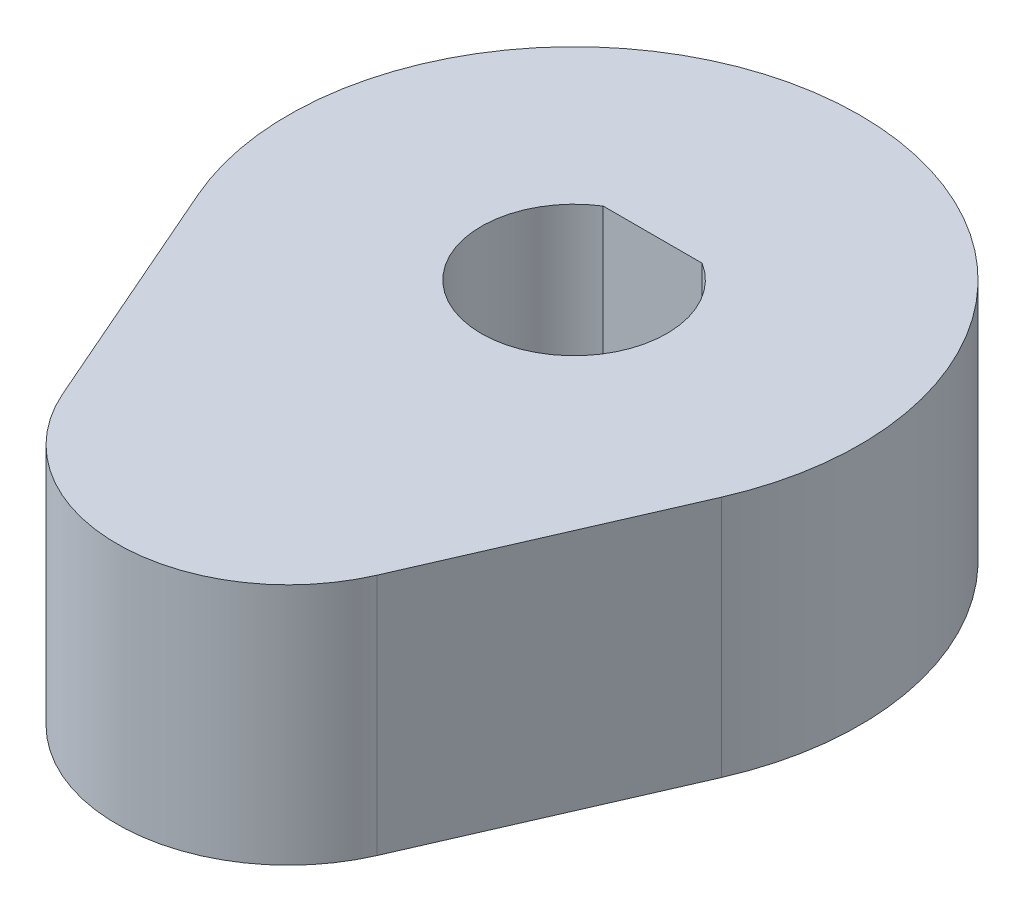
SolidWorks part; units mm, degrees
material "PET"
ref_plane "Front Plane" through (0, 0, 0) normal (0, 0, 1) x (1, 0, 0)
ref_plane "Top Plane" through (0, 0, 0) normal (0, 1, 0) x (1, 0, 0)
ref_plane "Right Plane" through (0, 0, 0) normal (1, 0, 0) x (0, 0, -1)
sketch "Sketch1" plane through (0, 0, 0) normal (0, 1, 0) x (1, 0, 0)
  line L0 (1.6583, 2.5) -> (-1.6583, 2.5) construction
  line L6 (0, 0) -> (0, -10) construction
  line L7 (-9.1652, -4) -> (-5.4991, -12.4)
  line L8 (9.1652, -4) -> (5.4991, -12.4)
  line L9 (1.732, 2.75) -> (-1.732, 2.75)
  arc A0 (-1.6583, 2.5) -> (1.6583, 2.5) centre (0, 0) ccw construction
  arc A3 (9.1652, -4) -> (-9.1652, -4) centre (0, 0) ccw
  arc A4 (-5.4991, -12.4) -> (5.4991, -12.4) centre (0, -10) ccw
  arc A5 (-1.732, 2.75) -> (1.732, 2.75) centre (0, 0) ccw
  dimension "D1" = 6
  dimension "D4" = 12
  dimension "D3" = 20
  dimension "D2" = 2.5
  dimension "D5" = 10
  dimension "D6" = 0.25
extrude "Boss-Extrude1" add sketch "Sketch1" along normal blind 8.5
